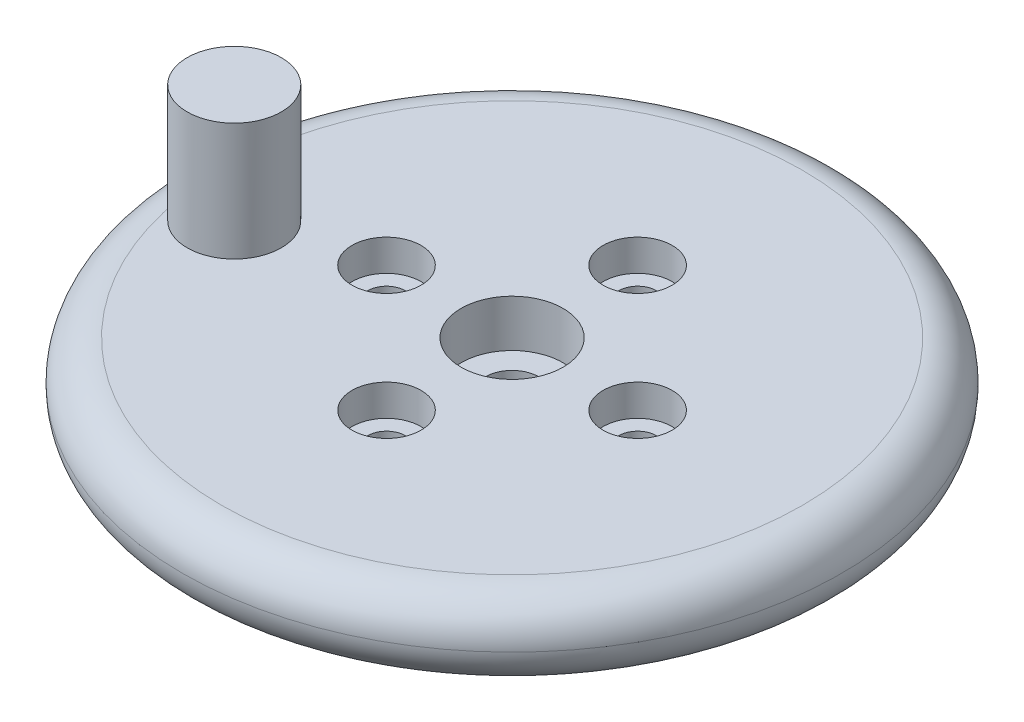
SolidWorks part; units mm, degrees
ref_plane "Front Plane" through (0, 0, 0) normal (0, 0, 1) x (1, 0, 0)
ref_plane "Top Plane" through (0, 0, 0) normal (0, 1, 0) x (1, 0, 0)
ref_plane "Right Plane" through (0, 0, 0) normal (1, 0, 0) x (0, 0, -1)
sketch "Sketch1" plane through (0, 0, 0) normal (0, 1, 0) x (1, 0, 0)
  circle A0 centre (0, 0) radius 21
  dimension "D1" = 42
extrude "Boss-Extrude1" add sketch "Sketch1" along normal blind 5
fillet "Fillet1" radius 2.5 2 edges at (0, 0, 21) (0, 5, 21)
sketch "Sketch2" plane through (0, 5, 0) normal (0, 1, 0) x (1, 0, 0)
  circle A0 centre (-15.315, -2.3879) radius 3
  circle A1 centre (0, 0) radius 18.5 construction
  dimension "D1" = 6
extrude "Boss-Extrude2" add sketch "Sketch2" along normal blind 7.5
hole_wizard "CBORE for M3 SHCS1" positions "Sketch7" profile "Sketch8" counterbore size "M3" standard "ANSI Metric" end condition through all
sketch "Sketch7" plane through (0, 5, 0) normal (0, 1, 0) x (1, 0, 0)
  point P0 (0, 0)
sketch "Sketch8" plane through (0, 5, 0) normal (1, 0, 0) x (0, 0, 1)
  line L0 (0, 0) -> (0, 5)
  line L1 (0, 5) -> (1.7, 5)
  line L3 (1.7, 5) -> (1.7, 3)
  line L4 (1.7, 3) -> (3.25, 3)
  line L5 (3.25, 3) -> (3.25, 0)
  line L7 (3.25, 0) -> (0, 0)
  line L11 (0, -6.35) -> (0, 107.95) construction
  dimension "Thru Hole Dia." = 3.4
  dimension "Thru Hole Depth" = 5
  dimension "C'Bore Dia." = 6.5
  dimension "C'Bore Depth" = 3
sketch "Sketch10" plane through (0, 0, 0) normal (0, 0, 1) x (1, 0, 0)
  line L0 (8, 5) -> (8, 0)
  line L1 (18.5, 5) -> (-18.5, 5) construction
  line L2 (-18.5, 0) -> (18.5, 0) construction
  line L3 (8, 0) -> (9.2, 0)
  line L4 (9.2, 0) -> (9.2, 3)
  line L5 (9.2, 3) -> (10.2, 3)
  line L6 (10.2, 3) -> (10.2, 5)
  line L7 (10.2, 5) -> (8, 5)
  dimension "D1" = 2
  dimension "D2" = 2.2
  dimension "D3" = 1.2
  dimension "D4" = 8
revolve "CBORe for M2" cut sketch "Sketch10" angle 360 about L0
pattern_circular "CirPattern1" count 4 over 360 about axis through (0, 5, 0) along (0, 1, 0) of "CBORe for M2"
